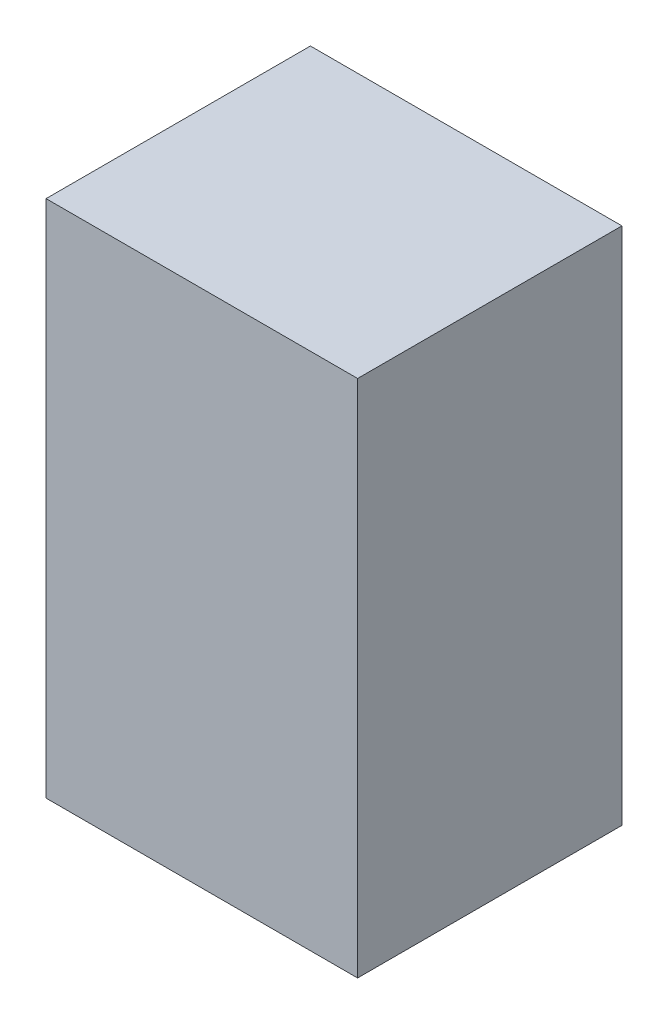
SolidWorks part; units mm, degrees
ref_plane "Front" through (0, 0, 0) normal (0, 0, 1) x (1, 0, 0)
ref_plane "Top" through (0, 0, 0) normal (0, 1, 0) x (1, 0, 0)
ref_plane "Right" through (0, 0, 0) normal (1, 0, 0) x (0, 0, -1)
sketch "Sketch1" plane through (0, 0, 0) normal (0, 1, 0) x (1, 0, 0)
  line L1 (0, 0) -> (838.2, 0)
  line L2 (0, 0) -> (0, 711.2)
  line L3 (0, 711.2) -> (838.2, 711.2)
  line L4 (838.2, 0) -> (838.2, 711.2)
  line L5 (0, 0) -> (838.2, 711.2) construction
  line L6 (0, 711.2) -> (838.2, 0) construction
  point P4 (419.1, 355.6)
  dimension "D1" = 711.2
  dimension "D2" = 838.2
extrude "Boss-Extrude1" add sketch "Sketch1" along normal blind 1397
shell "Shell1" thickness 2.54 removed face at (419.1, 0, -355.6)
ref_plane "Max_Bumper_Height" through (0, 177.8, 0) normal (0, 1, 0) x (1, 0, 0)
